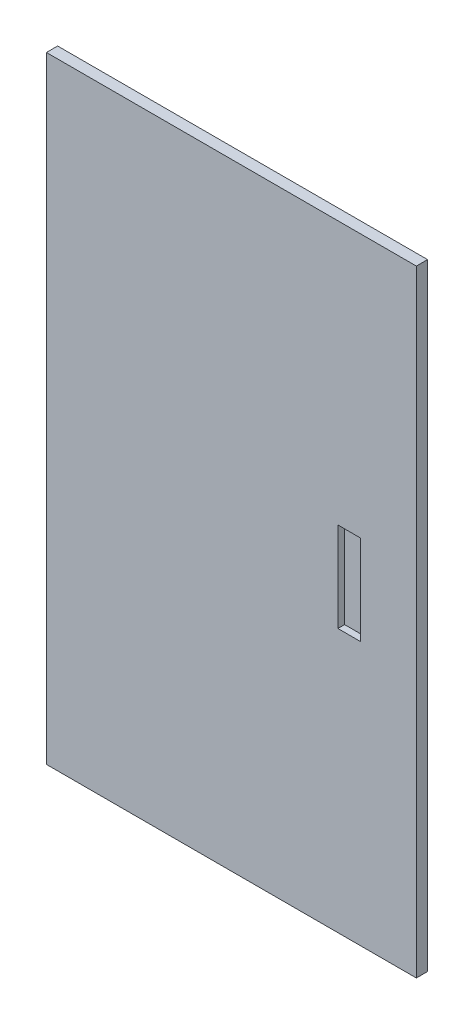
SolidWorks part; units mm, degrees
ref_plane "Front Plane" through (0, 0, 0) normal (0, 0, 1) x (1, 0, 0)
ref_plane "Top Plane" through (0, 0, 0) normal (0, 1, 0) x (1, 0, 0)
ref_plane "Right Plane" through (0, 0, 0) normal (1, 0, 0) x (0, 0, -1)
sketch "Sketch1" plane through (0, 0, 0) normal (0, 0, 1) x (1, 0, 0)
  line L1 (-209.55, -349.25) -> (209.55, -349.25)
  line L2 (-209.55, -349.25) -> (-209.55, 349.25)
  line L3 (-209.55, 349.25) -> (209.55, 349.25)
  line L4 (209.55, -349.25) -> (209.55, 349.25)
  line L5 (-209.55, -349.25) -> (209.55, 349.25) construction
  line L6 (-209.55, 349.25) -> (209.55, -349.25) construction
  point P0 (0, 0)
  dimension "D1" = 419.1
  dimension "D2" = 698.5
extrude "Boss-Extrude1" add sketch "Sketch1" along normal blind 12.7
sketch "Sketch2" plane through (0, 0, 12.7) normal (0, 0, 1) x (1, 0, 0)
  line L0 (-209.55, 0) -> (209.55, 0) construction
  line L1 (-209.55, 349.25) -> (-209.55, -349.25) construction
  line L2 (209.55, -349.25) -> (209.55, 349.25) construction
  line L4 (120.65, -50.8) -> (158.75, -50.8)
  line L5 (120.65, -50.8) -> (120.65, 50.8)
  line L6 (120.65, 50.8) -> (158.75, 50.8)
  line L7 (158.75, -50.8) -> (158.75, 50.8)
  line L8 (120.65, -50.8) -> (158.75, 50.8) construction
  line L9 (120.65, 50.8) -> (158.75, -50.8) construction
  point P6 (139.7, 0)
  dimension "D1" = 50.8
  dimension "D2" = 101.6
  dimension "D3" = 38.1
extrude "Cut-Extrude1" cut sketch "Sketch2" against normal blind 7.62
sketch "Sketch3" plane through (0, 0, 12.7) normal (0, 0, 1) x (1, 0, 0)
  line L0 (120.65, -50.8) -> (158.75, -50.8) construction
  line L1 (158.75, 50.8) -> (146.05, 50.8)
  line L2 (158.75, 50.8) -> (158.75, -50.8)
  line L3 (158.75, -50.8) -> (146.05, -50.8)
  line L4 (146.05, 50.8) -> (146.05, -50.8)
  dimension "D1" = 12.7
extrude "Boss-Extrude2" add sketch "Sketch3" against normal blind 2.54
fillet "Fillet1" radius 2.54 1 edges at (146.05, 0, 10.16)
